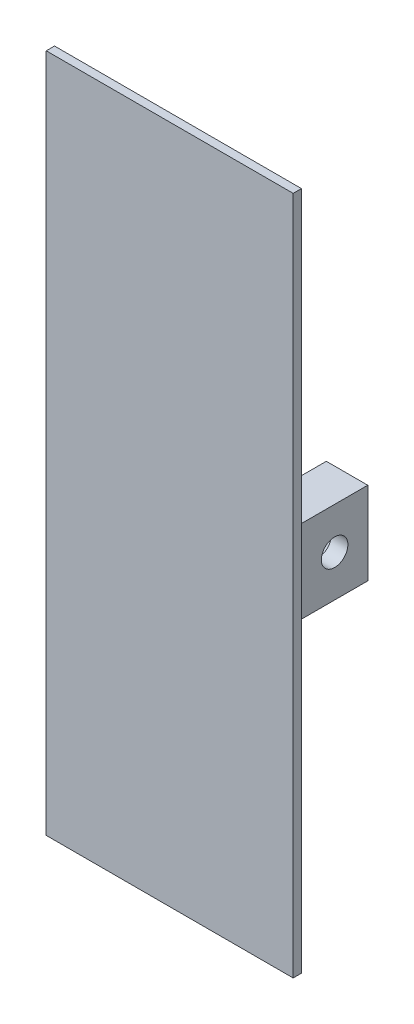
SolidWorks part; units mm, degrees
ref_plane "Front Plane" through (0, 0, 0) normal (0, 0, 1) x (1, 0, 0)
ref_plane "Top Plane" through (0, 0, 0) normal (0, 1, 0) x (1, 0, 0)
ref_plane "Right Plane" through (0, 0, 0) normal (1, 0, 0) x (0, 0, -1)
sketch "Sketch1" plane through (0, 0, 0) normal (0, 0, 1) x (1, 0, 0)
  line L1 (14.9, -41) -> (-14.9, -41)
  line L2 (14.9, -41) -> (14.9, 41)
  line L3 (14.9, 41) -> (-14.9, 41)
  line L4 (-14.9, -41) -> (-14.9, 41)
  line L5 (14.9, -41) -> (-14.9, 41) construction
  line L6 (14.9, 41) -> (-14.9, -41) construction
  point P0 (0, 0)
  dimension "D1" = 82
  dimension "D2" = 29.8
extrude "Boss-Extrude1" add sketch "Sketch1" along normal blind 1
sketch "Sketch2" plane through (0, 0, 0) normal (0, 0, -1) x (-1, 0, 0)
  line L0 (-14.9, -41) -> (-14.9, 41) construction
  line L1 (13.9, -39.95) -> (-13.9, -39.95)
  line L2 (13.9, -39.95) -> (13.9, 39.95)
  line L3 (13.9, 39.95) -> (-13.9, 39.95)
  line L4 (-13.9, -39.95) -> (-13.9, 39.95)
  line L5 (13.9, -39.95) -> (-13.9, 39.95) construction
  line L6 (13.9, 39.95) -> (-13.9, -39.95) construction
  point P0 (0, 0)
  dimension "D1" = 79.9
  dimension "D2" = 1
extrude "Boss-Extrude2" add sketch "Sketch2" along normal blind 0.001
sketch "Sketch3" plane through (0, 0, 0) normal (0, 0, -1) x (-1, 0, 0)
  line L0 (-13.9, -39.95) -> (-13.9, 39.95) construction
  line L1 (-13.9, 5) -> (-8.9, 5)
  line L2 (-13.9, 5) -> (-13.9, -5)
  line L3 (-13.9, -5) -> (-8.9, -5)
  line L4 (-8.9, 5) -> (-8.9, -5)
  dimension "D1" = 5
  dimension "D2" = 10
  dimension "D3" = 5
extrude "Boss-Extrude3" add sketch "Sketch3" along normal blind 9
sketch "Sketch4" plane through (8.9, 0, 0) normal (-1, 0, 0) x (0, 0, 1)
  line L0 (-9, 5) -> (-0.001, 5) construction
  line L1 (-3.3834, 2.8) -> (-6.6166, 2.8)
  line L2 (-6.6166, 2.8) -> (-8.2332, 0)
  line L3 (-8.2332, 0) -> (-6.6166, -2.8)
  line L4 (-6.6166, -2.8) -> (-3.3834, -2.8)
  line L5 (-3.3834, -2.8) -> (-1.7668, 0)
  line L6 (-1.7668, 0) -> (-3.3834, 2.8)
  line L8 (1, 41) -> (1, -41) construction
  circle A0 centre (-5, 0) radius 2.8 construction
  dimension "D1" = 5.6
  dimension "D2" = 6
extrude "Cut-Extrude1" cut sketch "Sketch4" against normal blind 3
sketch "Sketch5" plane through (11.9, 0, 0) normal (-1, 0, 0) x (0, 0, 1)
  line L1 (-9, 5) -> (-0.001, 5) construction
  line L2 (0, -5) -> (0, 5) construction
  circle A0 centre (-5, 0) radius 1.6
  dimension "D1" = 5
  dimension "D2" = 5
  dimension "D3" = 3.2
extrude "Cut-Extrude2" cut sketch "Sketch5" against normal up to surface (2 mm away) up to face at (13.9, 0, -2.2505)
chamfer "Chamfer1" distance 1.5 angle 45 1 edges at (8.9, 0, -0.001)
